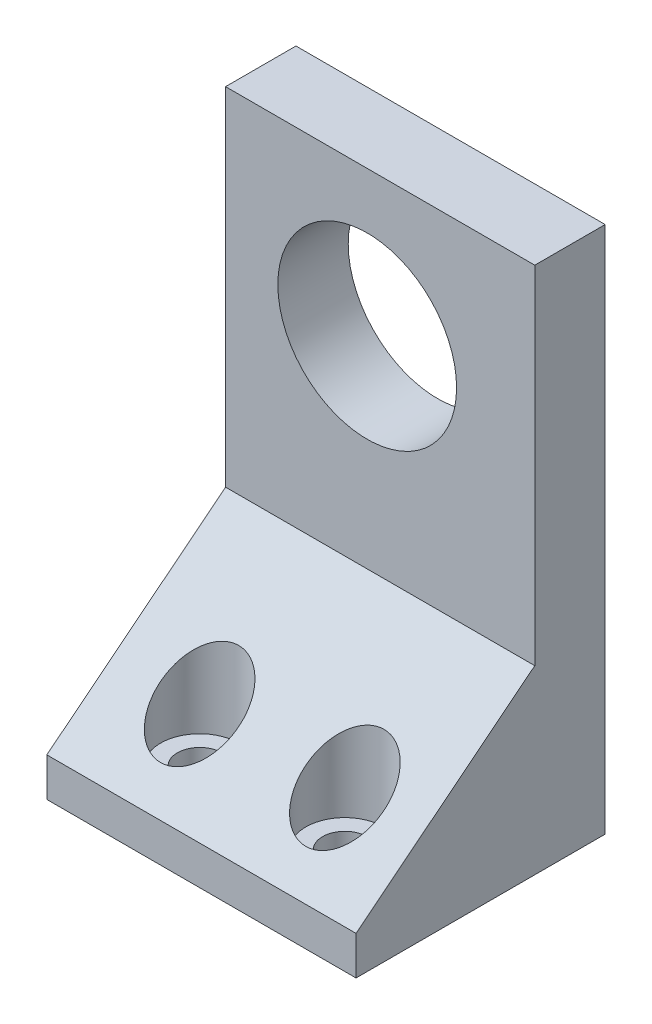
SolidWorks part; units mm, degrees
material "ABS"
ref_plane "Front Plane" through (0, 0, 0) normal (0, 0, 1) x (1, 0, 0)
ref_plane "Top Plane" through (0, 0, 0) normal (0, 1, 0) x (1, 0, 0)
ref_plane "Right Plane" through (0, 0, 0) normal (1, 0, 0) x (0, 0, -1)
sketch "Sketch1" plane through (0, 0, 0) normal (0, 0, 1) x (1, 0, 0)
  line L1 (-76.1871, 64.9281) -> (16.8129, 64.9281)
  line L2 (-76.1871, 64.9281) -> (-76.1871, -35.0719)
  line L3 (-76.1871, -35.0719) -> (16.8129, -35.0719)
  line L4 (16.8129, 64.9281) -> (16.8129, -35.0719)
  dimension "D1" = 93
  dimension "D2" = 100
extrude "Boss-Extrude2" add sketch "Sketch1" along normal blind 10 contours L1 L4 L3 L2
sketch "Sketch3" plane through (0, 0, 0) normal (0, 0, -1) x (-1, 0, 0)
  line L0 (76.1871, -35.0719) -> (-16.8129, -35.0719) construction
  line L1 (-16.8129, 64.9281) -> (-6.8129, 64.9281)
  line L2 (-16.8129, 64.9281) -> (-16.8129, -35.0719)
  line L3 (-16.8129, -35.0719) -> (-6.8129, -35.0719)
  line L4 (-6.8129, 64.9281) -> (-6.8129, -35.0719)
  line L5 (-16.8129, 64.9281) -> (-16.8129, -35.0719) construction
  dimension "D1" = 0
  dimension "D2" = 0
  dimension "D3" = 10
  dimension "D4" = 100
sketch "Sketch4" plane through (16.8129, 0, 0) normal (1, 0, 0) x (0, 0, -1)
  line L0 (-10, 64.9281) -> (-10, -35.0719) construction
  line L1 (-10, -5.0719) -> (0.01, -5.0719)
  line L2 (-10, -5.0719) -> (-10, -20.0719)
  line L3 (-10, -20.0719) -> (0.01, -20.0719)
  line L4 (0.01, -5.0719) -> (0.01, -20.0719)
  line L6 (-10, -35.0719) -> (0, -35.0719) construction
  dimension "D1" = 15
  dimension "D2" = 15
extrude "Boss-Extrude4" add sketch "Sketch4" along normal blind 24
sketch "Sketch5" plane through (0, -5.0719, 0) normal (0, 1, 0) x (1, 0, 0)
  line L0 (40.8129, -10) -> (16.8129, -10) construction
  line L2 (16.8129, 0) -> (16.8129, -10) construction
  circle A0 centre (26.8129, -5) radius 2
  dimension "D2" = 4
  dimension "D3" = 10
  dimension "D1" = 5
extrude "Cut-Extrude1" cut sketch "Sketch5" against normal blind 50
sketch "Sketch6" plane through (0, 0, 10) normal (0, 0, -1) x (-1, 0, 0)
  line L2 (76.1871, -35.0719) -> (-16.8129, -35.0719) construction
  line L3 (-16.8129, 64.9281) -> (-16.8129, -35.0719) construction
  circle A0 centre (-1.8129, -24.5719) radius 7.5
  dimension "D1" = 15
  dimension "D2" = 10.5
  dimension "D3" = 15
sketch "Sketch7" plane through (0, 0, 0) normal (0, 0, -1) x (-1, 0, 0)
  circle A0 centre (24.1871, 36.9281) radius 11
  circle A1 centre (24.1871, 36.9281) radius 9.3 construction
  dimension "D1" = 22
extrude "Cut-Extrude3" cut sketch "Sketch7" against normal blind 50
sketch "Sketch14" plane through (0, 0, 10) normal (0, 0, 1) x (1, 0, 0)
  line L0 (16.8129, 64.9281) -> (16.8129, -5.0719) construction
  line L1 (-44.6871, 15.7891) -> (16.8129, 15.7891)
  line L2 (-44.6871, 15.7891) -> (-44.6871, 57.7891)
  line L3 (-44.6871, 57.7891) -> (16.8129, 57.7891)
  line L4 (16.8129, 15.7891) -> (16.8129, 57.7891)
  dimension "D1" = 42
  dimension "D3" = 61.5
extrude "Cut-Extrude8" cut sketch "Sketch14" against normal blind 4
sketch "Sketch15" plane through (0, 0, 0) normal (0, 0, -1) x (-1, 0, 0)
  circle A0 centre (24.1871, 36.9281) radius 10
  circle A1 centre (24.1871, 36.9281) radius 11 construction
  dimension "D1" = 20
  dimension "D2" = 0
sketch "Sketch16" plane through (0, 0, 10) normal (0, 0, 1) x (1, 0, 0)
  line L0 (-43.6871, 56.9281) -> (14.3129, 56.9281) construction
  line L1 (-44.1871, 57.3281) -> (16.8129, 57.3281)
  line L2 (-44.1871, 57.3281) -> (-44.1871, 64.9281)
  line L3 (-44.1871, 64.9281) -> (16.8129, 64.9281)
  line L4 (16.8129, 57.3281) -> (16.8129, 64.9281)
  dimension "D1" = 0.4
sketch "Sketch17" plane through (0, 0, 10) normal (0, 0, 1) x (1, 0, 0)
  line L0 (16.8129, 15.7891) -> (16.8129, -5.0719) construction
  line L1 (-44.1871, 16.7281) -> (16.8129, 16.7281)
  line L2 (-44.1871, 16.7281) -> (-44.1871, -20.0719)
  line L3 (-44.1871, -20.0719) -> (16.8129, -20.0719)
  line L4 (16.8129, 16.7281) -> (16.8129, -20.0719)
  line L5 (-43.6871, 16.9281) -> (14.3129, 16.9281) construction
  line L6 (40.8129, -20.0719) -> (16.8129, -20.0719) construction
  line L9 (16.8129, -20.0719) -> (40.8129, -20.0719)
  line L10 (16.8129, -20.0719) -> (16.8129, -5.0719)
  line L11 (16.8129, -5.0719) -> (40.8129, -5.0719)
  line L12 (40.8129, -20.0719) -> (40.8129, -5.0719)
  line L13 (16.8129, -20.0719) -> (40.8129, -5.0719) construction
  line L14 (16.8129, -5.0719) -> (40.8129, -20.0719) construction
  point P16 (28.8129, -12.5719)
  dimension "D1" = 0.2
  dimension "D2" = 0
sketch "Sketch19" plane through (0, 0, 0) normal (0, 0, -1) x (-1, 0, 0)
  line L1 (-16.8129, 64.9281) -> (-16.8129, -35.0719) construction
  circle A0 centre (53.1871, 36.9281) radius 11
  circle A1 centre (24.1871, 36.9281) radius 10 construction
  dimension "D1" = 22
  dimension "D3" = 0
  dimension "D2" = 70
extrude "Cut-Extrude11" cut sketch "Sketch19" against normal blind 15
sketch "Sketch20" plane through (0, 0, 6) normal (0, 0, 1) x (1, 0, 0)
  circle A0 centre (-34.6871, 50.9281) radius 2
  circle A1 centre (5.3129, 50.9281) radius 2
  circle A2 centre (-34.6871, 22.9281) radius 2
  circle A3 centre (5.3129, 22.9281) radius 2
  arc A5 (-27.0471, 34.1316) -> (-27.0471, 39.7246) centre (-24.1871, 36.9281) ccw construction
  circle A6 centre (-24.1871, 36.9281) radius 11 construction
  dimension "D1" = 4
  dimension "D2" = 4
  dimension "D3" = 4
  dimension "D4" = 4
  dimension "D5" = 0
  dimension "D6" = 28
  dimension "D7" = 0
  dimension "D8" = 40
  dimension "D9" = 14
  dimension "D10" = 10.5
  dimension "D11" = 28
  dimension "D12" = 40
extrude "Cut-Extrude12" cut sketch "Sketch20" against normal blind 10
sketch "Sketch8" plane through (0, 64.9281, 0) normal (0, 1, 0) x (1, 0, 0)
  line L0 (-76.1871, -10) -> (16.8129, -10) construction
  line L5 (16.8129, 0) -> (12.3014, -10) construction
  line L6 (16.8129, -10) -> (7.8859, 0) construction
  line L8 (16.8129, -10) -> (16.8129, 0) construction
  line L9 (-76.1871, 0) -> (16.8129, 0) construction
  circle A0 centre (11.8129, -7) radius 1.4
  circle A1 centre (-13.1871, -7) radius 1.4
  point P4 (13.816, -6.6429)
  dimension "D1" = 25
  dimension "D2" = 5
  dimension "D3" = 2.8
  dimension "D4" = 7
  dimension "D5" = 7
sketch "Sketch21" plane through (0, 0, 0) normal (0, 0, -1) x (-1, 0, 0)
  line L1 (76.1871, 64.9281) -> (36.1871, 64.9281)
  line L2 (76.1871, 64.9281) -> (76.1871, 58.9281)
  line L3 (76.1871, 58.9281) -> (36.1871, 58.9281)
  line L4 (36.1871, 64.9281) -> (36.1871, 58.9281)
  dimension "D1" = 6
  dimension "D2" = 40
extrude "Boss-Extrude5" add sketch "Sketch21" along normal blind 27
sketch "Sketch22" plane through (0, 58.9281, 0) normal (0, -1, 0) x (1, 0, 0)
  line L0 (-76.1871, -27) -> (-76.1871, 0) construction
  line L1 (-36.1871, -27) -> (-76.1871, -27)
  line L2 (-36.1871, -27) -> (-36.1871, -20.7)
  line L3 (-36.1871, -20.7) -> (-76.1871, -20.7)
  line L4 (-76.1871, -27) -> (-76.1871, -20.7)
  dimension "D1" = 6.3
extrude "Boss-Extrude7" add sketch "Sketch22" along normal blind 40
sketch "Sketch23" plane through (0, 0, 10) normal (0, 0, 1) x (1, 0, 0)
  circle A0 centre (-53.1871, 36.9281) radius 8
  arc A1 (-44.6871, 43.9102) -> (-44.6871, 29.9459) centre (-53.1871, 36.9281) ccw construction
  dimension "D1" = 16
  dimension "D2" = 0
extrude "Cut-Extrude13" cut sketch "Sketch23" against normal blind 40
sketch "Sketch24" plane through (0, 0, 10) normal (0, 0, 1) x (1, 0, 0)
  line L1 (-76.1871, -35.0719) -> (42.0908, -35.0719)
  line L2 (-76.1871, -35.0719) -> (-76.1871, 6.7281)
  line L3 (-76.1871, 6.7281) -> (42.0908, 6.7281)
  line L4 (42.0908, -35.0719) -> (42.0908, 6.7281)
  dimension "D1" = 41.8
extrude "Cut-Extrude14" cut sketch "Sketch24" against normal blind 40
sketch "Sketch25" plane through (0, 0, 10) normal (0, 0, 1) x (1, 0, 0)
  line L5 (-44.6871, 29.9459) -> (-44.6871, 15.7891) construction
  line L6 (-76.1871, 6.7281) -> (-44.6871, 6.7281)
  line L7 (-76.1871, 6.7281) -> (-76.1871, 29.9281)
  line L8 (-76.1871, 29.9281) -> (-44.6871, 29.9281)
  line L9 (-44.6871, 6.7281) -> (-44.6871, 29.9281)
  arc A2 (-44.6871, 43.9102) -> (-44.6871, 29.9459) centre (-53.1871, 36.9281) ccw construction
  dimension "D1" = 7
extrude "Cut-Extrude15" cut sketch "Sketch25" against normal blind 20
sketch "Sketch26" plane through (0, 0, 6) normal (0, 0, 1) x (1, 0, 0)
  line L1 (-44.6871, 15.7891) -> (-36.2375, 15.7891)
  line L2 (-44.6871, 15.7891) -> (-44.6871, 21.6647)
  line L3 (-44.6871, 21.6647) -> (-36.2375, 21.6647)
  line L4 (-36.2375, 15.7891) -> (-36.2375, 21.6647)
  line L5 (-44.6871, 57.7891) -> (-36.2375, 57.7891)
  line L6 (-44.6871, 57.7891) -> (-44.6871, 52.1914)
  line L7 (-44.6871, 52.1914) -> (-36.2375, 52.1914)
  line L8 (-36.2375, 57.7891) -> (-36.2375, 52.1914)
  line L9 (6.8634, 52.1914) -> (14.3021, 52.1914)
  line L10 (6.8634, 52.1914) -> (6.8634, 57.7891)
  line L11 (6.8634, 57.7891) -> (14.3021, 57.7891)
  line L12 (14.3021, 52.1914) -> (14.3021, 57.7891)
  line L13 (6.8634, 20.9281) -> (14.3021, 20.9281)
  line L14 (6.8634, 20.9281) -> (6.8634, 15.7891)
  line L15 (6.8634, 15.7891) -> (14.3021, 15.7891)
  line L16 (14.3021, 20.9281) -> (14.3021, 15.7891)
  circle A0 centre (-34.6871, 22.9281) radius 2 construction
  circle A1 centre (-34.6871, 50.9281) radius 2 construction
  circle A2 centre (5.3129, 50.9281) radius 2 construction
  circle A3 centre (5.3129, 22.9281) radius 4
  circle A4 centre (5.3129, 50.9281) radius 4
  circle A5 centre (-34.6871, 50.9281) radius 4
  circle A6 centre (-34.6871, 22.9281) radius 4
  circle A7 centre (5.3129, 50.9281) radius 4
  circle A8 centre (5.3129, 22.9281) radius 4
  circle A9 centre (-34.6871, 50.9281) radius 4
  circle A10 centre (-34.6871, 22.9281) radius 4
  line M5 (-44.6871, 57.7891) -> (-44.6871, 43.9102)
  line M8 (-44.6871, 29.9281) -> (-44.6871, 15.7891)
  line M9 (-44.6871, 15.7891) -> (16.8129, 15.7891)
  line M11 (16.8129, 57.7891) -> (-44.6871, 57.7891)
  dimension "D1" = 8
  dimension "D2" = 8
  dimension "D3" = 8
  dimension "D4" = 8
extrude "Cut-Extrude18" cut sketch "Sketch26" against normal blind 3 contours A4 L9 L12 L10 M11 | A3 L14 L16 L13 M9 | A5 L8 L7 M11 M5 | A6 L3 L4 M8 M9 region at (-40.7189, 18.5733, 6) region at (10.7466, 18.2528, 6) region at (10.8466, 55.1634, 6) region at (-40.7326, 55.141, 6)
sketch "Sketch27" plane through (0, 0, 6) normal (0, 0, 1) x (1, 0, 0)
  circle A0 centre (5.3129, 50.9281) radius 4.1
  circle A1 centre (5.3129, 22.9281) radius 4
  circle A2 centre (-34.6871, 50.9281) radius 4.1
  circle A3 centre (-34.6871, 22.9281) radius 4.1
  dimension "D1" = 8.2
  dimension "D2" = 8.2
  dimension "D3" = 8
  dimension "D4" = 8.2
extrude "Cut-Extrude29" cut sketch "Sketch27" against normal blind 3
sketch "Sketch28" plane through (0, 0, 0) normal (0, 0, -1) x (-1, 0, 0)
  line L5 (-16.8129, 6.7281) -> (44.6871, 6.7281) construction
  line L6 (-16.8129, 64.9281) -> (12.6871, 64.9281)
  line L7 (-16.8129, 64.9281) -> (-16.8129, 6.7281)
  line L8 (-16.8129, 6.7281) -> (12.6871, 6.7281)
  line L9 (12.6871, 64.9281) -> (12.6871, 6.7281)
  circle A1 centre (34.6871, 22.9281) radius 2 construction
  dimension "D1" = 22
extrude "Cut-Extrude30" cut sketch "Sketch28" against normal blind 23
sketch "Sketch29" plane through (0, 15.7891, 0) normal (0, 1, 0) x (1, 0, 0)
  line L1 (-44.6871, -10) -> (-12.6871, -10)
  line L2 (-44.6871, -10) -> (-44.6871, -6)
  line L3 (-44.6871, -6) -> (-12.6871, -6)
  line L4 (-12.6871, -10) -> (-12.6871, -6)
extrude "Cut-Extrude31" cut sketch "Sketch29" against normal blind 23
sketch "Sketch31" plane through (0, 6.7281, 0) normal (0, -1, 0) x (1, 0, 0)
  line L1 (-44.6871, 6) -> (-12.6871, 6)
  line L2 (-44.6871, 6) -> (-44.6871, 0)
  line L3 (-44.6871, 0) -> (-12.6871, 0)
  line L4 (-12.6871, 6) -> (-12.6871, 0)
extrude "Boss-Extrude9" add sketch "Sketch31" along normal blind 6.6
sketch "Sketch32" plane through (0, 0, 6) normal (0, 0, 1) x (1, 0, 0)
  line L0 (-12.6871, 0.1281) -> (-12.6871, 57.7891) construction
  line L1 (-44.6871, 0.1281) -> (-12.6871, 0.1281)
  line L2 (-44.6871, 0.1281) -> (-44.6871, 6.1281)
  line L3 (-44.6871, 6.1281) -> (-12.6871, 6.1281)
  line L4 (-12.6871, 0.1281) -> (-12.6871, 6.1281)
  dimension "D1" = 6
extrude "Boss-Extrude10" add sketch "Sketch32" along normal blind 10
sketch "Sketch33" plane through (0, 6.1281, 0) normal (0, 1, 0) x (1, 0, 0)
  line L0 (-12.6871, -16) -> (-44.6871, -16) construction
  line L1 (-44.6871, -16) -> (-44.6871, -6) construction
  line L2 (-12.6871, -16) -> (-12.6871, -6) construction
  circle A0 centre (-37.6871, -11) radius 2
  circle A1 centre (-19.6871, -11) radius 2
  point P8 (-44.6871, -11)
  dimension "D1" = 4
  dimension "D2" = 4
  dimension "D3" = 0
  dimension "D4" = 5
  dimension "D5" = 7
  dimension "D6" = 7
extrude "Cut-Extrude32" cut sketch "Sketch33" against normal blind 10
sketch "Sketch34" plane through (-12.6871, 0, 0) normal (1, 0, 0) x (0, 0, -1)
  line L0 (-16, 6.1281) -> (-6, 6.1281)
  line L1 (-6, 6.1281) -> (-6, 14.0584)
  line L2 (-6, 6.1281) -> (-6, 57.7891) construction
  line L3 (-6, 14.0584) -> (-16, 6.1281)
extrude "Boss-Extrude11" add sketch "Sketch34" against normal up to vertex (32 mm away) up to point (-44.6871, 29.9281, 6)
sketch "Sketch35" plane through (0, 6.1281, 0) normal (0, -1, 0) x (1, 0, 0)
  circle A0 centre (-19.6871, 11) radius 3.5
  circle A1 centre (-37.6871, 11) radius 3.5
  dimension "D1" = 7
  dimension "D2" = 7
extrude "Cut-Extrude33" cut sketch "Sketch35" against normal blind 10
sketch "Sketch36" plane through (0, 18.9281, 0) normal (0, -1, 0) x (1, 0, 0)
  line L1 (-76.1871, -20.7) -> (-36.1871, -20.7)
  line L2 (-76.1871, -20.7) -> (-76.1871, -27)
  line L3 (-76.1871, -27) -> (-36.1871, -27)
  line L4 (-36.1871, -20.7) -> (-36.1871, -27)
extrude "Boss-Extrude12" add sketch "Sketch36" along normal up to vertex (18.8 mm away) up to point (-44.6871, 0.1281, 0)
sketch "Sketch37" plane through (0, 0, -20.7) normal (0, 0, 1) x (1, 0, 0)
  line L0 (-76.1871, 0.1281) -> (-76.1871, 58.9281) construction
  line L1 (-36.1871, 0.1281) -> (-76.1871, 0.1281)
  line L2 (-36.1871, 0.1281) -> (-36.1871, 6.1281)
  line L3 (-36.1871, 6.1281) -> (-76.1871, 6.1281)
  line L4 (-76.1871, 0.1281) -> (-76.1871, 6.1281)
  dimension "D1" = 6
extrude "Boss-Extrude13" add sketch "Sketch37" along normal blind 16
sketch "Sketch38" plane through (0, 6.1281, 0) normal (0, 1, 0) x (1, 0, 0)
  line L0 (-36.1871, 4.7) -> (-76.1871, 4.7) construction
  line L2 (-36.1871, 4.7) -> (-36.1871, 20.7) construction
  circle A0 centre (-58.1871, 10.7) radius 2
  circle A1 centre (-45.1871, 10.7) radius 2
  dimension "D1" = 4
  dimension "D2" = 4
  dimension "D3" = 6
  dimension "D4" = 13
  dimension "D5" = 9
  dimension "D6" = 6
extrude "Cut-Extrude34" cut sketch "Sketch38" against normal blind 16
sketch "Sketch39" plane through (-36.1871, 0, 0) normal (1, 0, 0) x (0, 0, -1)
  line L0 (4.7, 6.1281) -> (20.7, 18.8781)
  line L1 (20.7, 6.1281) -> (20.7, 58.9281) construction
  line L2 (20.7, 18.8781) -> (20.7, 6.1281)
  line L3 (20.7, 6.1281) -> (4.7, 6.1281)
extrude "Boss-Extrude14" add sketch "Sketch39" against normal up to vertex (40 mm away) up to point (-76.1871, 6.1281, -4.7)
sketch "Sketch40" plane through (0, 6.1281, 0) normal (0, -1, 0) x (1, 0, 0)
  circle A0 centre (-45.1871, -10.7) radius 3.5
  circle A1 centre (-58.1871, -10.7) radius 3.5
  dimension "D1" = 7
  dimension "D2" = 7
extrude "Cut-Extrude35" cut sketch "Sketch40" against normal blind 16
sketch "Sketch41" plane through (-12.6871, 0, 0) normal (1, 0, 0) x (0, 0, -1)
  line L1 (0, 64.9281) -> (-16, 64.9281)
  line L2 (0, 64.9281) -> (0, 0.1281)
  line L3 (0, 0.1281) -> (-16, 0.1281)
  line L4 (-16, 64.9281) -> (-16, 0.1281)
extrude "Cut-Extrude36" cut sketch "Sketch41" against normal blind 76
sketch "Sketch42" plane through (-36.1871, 0, 0) normal (1, 0, 0) x (0, 0, -1)
  line L0 (27, 64.9281) -> (0, 64.9281) construction
  line L1 (20.7, 58.9281) -> (0, 58.9281)
  line L2 (20.7, 58.9281) -> (20.7, 64.9281)
  line L3 (20.7, 64.9281) -> (0, 64.9281)
  line L4 (0, 58.9281) -> (0, 64.9281)
extrude "Cut-Extrude37" cut sketch "Sketch42" against normal blind 76
sketch "Sketch43" plane through (0, 0, -4.7) normal (0, 0, 1) x (1, 0, 0)
  line L1 (-76.1871, 0.1281) -> (-65.8661, 0.1281)
  line L2 (-76.1871, 0.1281) -> (-76.1871, 73.2032)
  line L3 (-76.1871, 73.2032) -> (-65.8661, 73.2032)
  line L4 (-65.8661, 0.1281) -> (-65.8661, 73.2032)
extrude "Cut-Extrude38" cut sketch "Sketch43" against normal blind 30
sketch "Sketch44" plane through (0, 0, -4.7) normal (0, 0, 1) x (1, 0, 0)
  line L1 (-36.1871, 0.1281) -> (-38.1871, 0.1281)
  line L2 (-36.1871, 0.1281) -> (-36.1871, 70.9113)
  line L3 (-36.1871, 70.9113) -> (-38.1871, 70.9113)
  line L4 (-38.1871, 0.1281) -> (-38.1871, 70.9113)
  dimension "D1" = 2
extrude "Cut-Extrude39" cut sketch "Sketch44" against normal blind 30
sketch "Sketch45" plane through (0, 0, -20.7) normal (0, 0, 1) x (1, 0, 0)
  line L0 (-65.8661, 64.9281) -> (-65.8661, 18.8781) construction
  line L1 (-38.1871, 64.9281) -> (-65.8661, 64.9281)
  line L2 (-38.1871, 64.9281) -> (-38.1871, 49.9281)
  line L3 (-38.1871, 49.9281) -> (-65.8661, 49.9281)
  line L4 (-65.8661, 64.9281) -> (-65.8661, 49.9281)
  circle A0 centre (-53.1871, 36.9281) radius 8 construction
  dimension "D1" = 13
extrude "Cut-Extrude40" cut sketch "Sketch45" against normal blind 30
sketch "Sketch46" plane through (0, 0, -4.7) normal (0, 0, 1) x (1, 0, 0)
  line L0 (-38.1871, 6.1281) -> (-38.1871, 0.1281) construction
  line L1 (-65.8661, 0.1281) -> (-38.1871, 0.1281)
  line L2 (-65.8661, 0.1281) -> (-65.8661, 2.6681)
  line L3 (-65.8661, 2.6681) -> (-38.1871, 2.6681)
  line L4 (-38.1871, 0.1281) -> (-38.1871, 2.6681)
  dimension "D1" = 2.54
extrude "Cut-Extrude41" cut sketch "Sketch46" against normal blind 110
